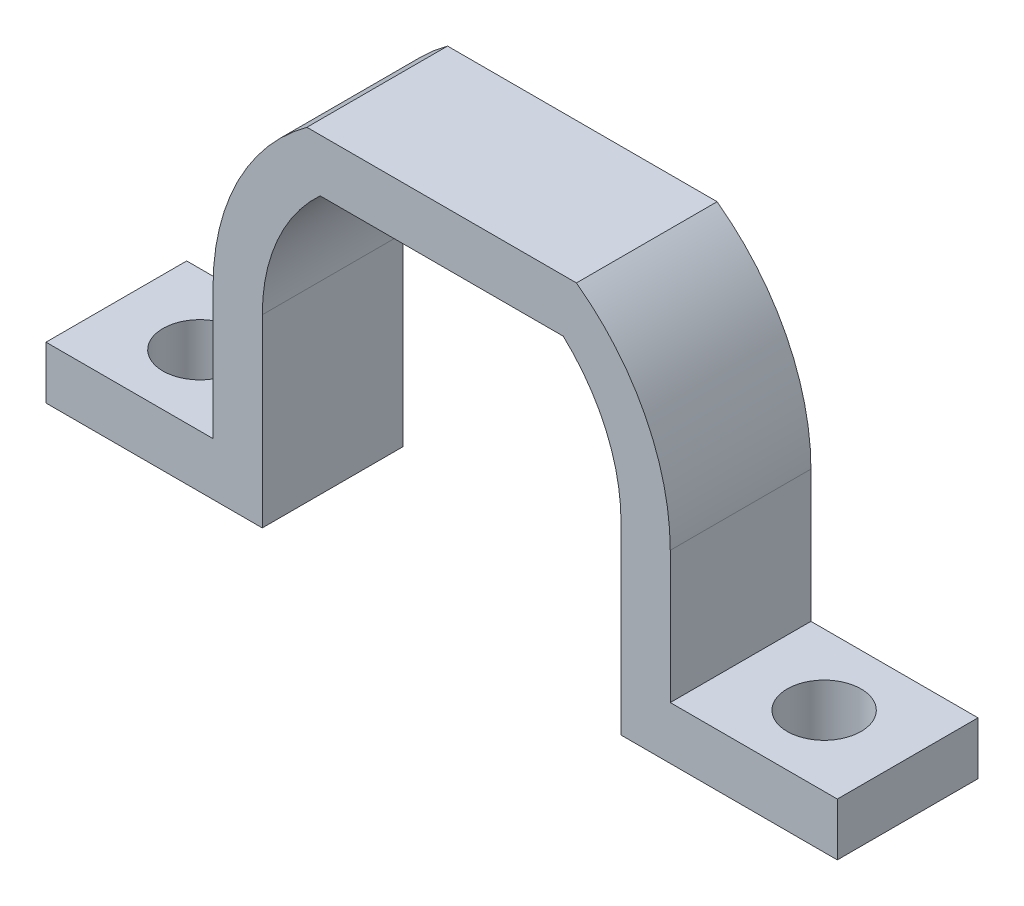
SolidWorks part; units mm, degrees
ref_plane "Front Plane" through (0, 0, 0) normal (0, 0, 1) x (1, 0, 0)
ref_plane "Top Plane" through (0, 0, 0) normal (0, 1, 0) x (1, 0, 0)
ref_plane "Right Plane" through (0, 0, 0) normal (1, 0, 0) x (0, 0, -1)
sketch "Sketch1" plane through (0, 0, 0) normal (0, 0, 1) x (1, 0, 0)
  line L0 (-6.913, 7.5) -> (6.913, 7.5)
  line L2 (-13, -7.5) -> (-22.5, -7.5)
  line L3 (-22.5, -7.5) -> (-22.5, -10.5)
  line L4 (-22.5, -10.5) -> (-10.2, -10.5)
  line L5 (22.5, -10.5) -> (22.5, -7.5)
  line L7 (13, -7.5) -> (22.5, -7.5)
  line L8 (-7.6649, 10.5) -> (7.6649, 10.5)
  line L9 (-13, 0) -> (-13, -7.5)
  line L10 (13, 0) -> (13, -7.5)
  line L12 (-10.2, 0) -> (-10.2, -10.5)
  line L13 (10.2, 0) -> (10.2, -10.5)
  line L14 (10.2, -10.5) -> (22.5, -10.5)
  arc A0 (-6.913, 7.5) -> (-10.2, 0) centre (0, 0) ccw
  arc A1 (10.2, 0) -> (6.913, 7.5) centre (0, 0) ccw
  arc A2 (-7.6649, 10.5) -> (-13, 0) centre (0, 0) ccw
  arc A3 (13, 0) -> (7.6649, 10.5) centre (0, 0) ccw
  dimension "D1" = 20.4
  dimension "D6" = 26
  dimension "D2" = 7.5
  dimension "D3" = 3
  dimension "D4" = 10.5
  dimension "D5" = 45
  dimension "D7" = 3
extrude "Clamp" add sketch "Sketch1" along normal blind 8
sketch "Sketch2" plane through (0, -7.5, 0) normal (0, 1, 0) x (1, 0, 0)
  line L0 (-22.5, -8) -> (-22.5, 0) construction
  line L1 (-13, 0) -> (-22.5, 0) construction
  line L2 (22.5, 0) -> (13, 0) construction
  circle A0 centre (-17.75, -4) radius 2.1
  circle A1 centre (17.75, -4) radius 2.1
  point P6 (-22.5, -4)
  point P9 (-17.75, 0)
  point P12 (17.75, 0)
  dimension "D1" = 4.2
extrude "Screw Hole" cut sketch "Sketch2" against normal through all
